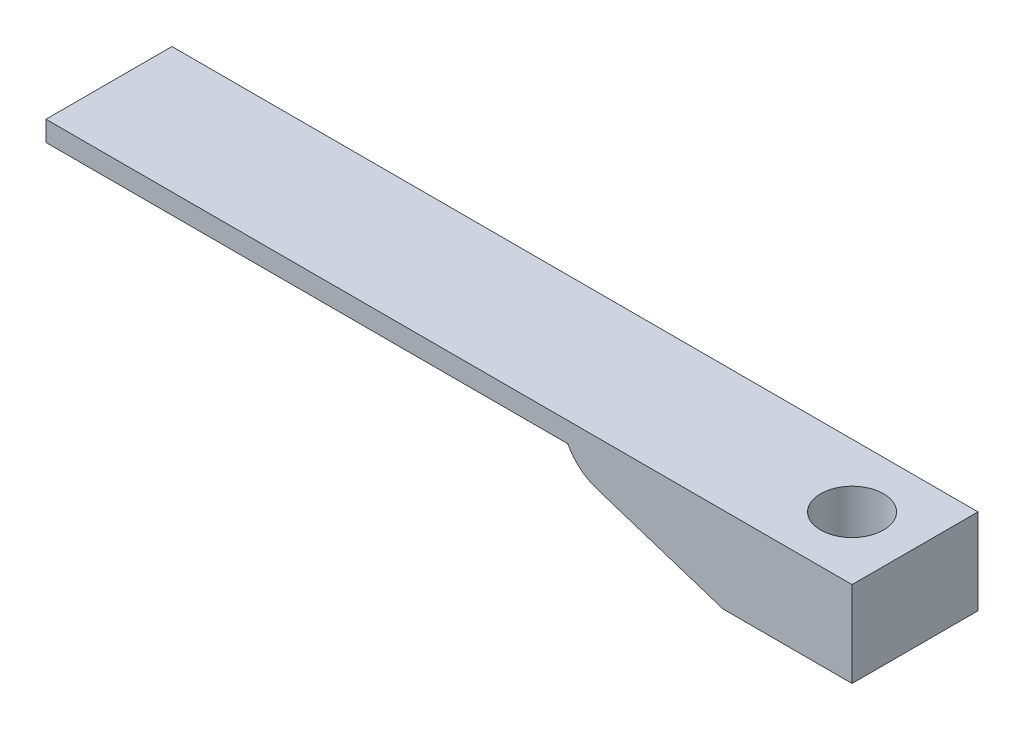
SolidWorks part; units mm, degrees
ref_plane "Front Plane" through (0, 0, 0) normal (0, 0, 1) x (1, 0, 0)
ref_plane "Top Plane" through (0, 0, 0) normal (0, 1, 0) x (1, 0, 0)
ref_plane "Right Plane" through (0, 0, 0) normal (1, 0, 0) x (0, 0, -1)
sketch "Sketch1" plane through (0, 0, 0) normal (0, 1, 0) x (1, 0, 0)
  line L1 (-80, 12.5) -> (80, 12.5)
  line L2 (-80, 12.5) -> (-80, -12.5)
  line L3 (-80, -12.5) -> (80, -12.5)
  line L4 (80, 12.5) -> (80, -12.5)
  line L5 (-80, 12.5) -> (80, -12.5) construction
  line L6 (-80, -12.5) -> (80, 12.5) construction
  circle A4 centre (67.5, 0) radius 6.25
  point P0 (0, 0)
  point P17 (80, 0)
  dimension "D3" = 12.5
  dimension "D4" = 12.5
  dimension "D1" = 25
  dimension "D2" = 160
extrude "Boss-Extrude1" add sketch "Sketch1" along normal blind 4 contours L3 L4 L1 L2 A4 | L3 region at (-2.1364, 0, 0)
sketch "Sketch2" plane through (0, 0, 0) normal (0, -1, 0) x (1, 0, 0)
  line L0 (23.59, 12.5) -> (23.59, -12.5)
  line L1 (-80, 12.5) -> (80, 12.5) construction
  line L2 (-80, -12.5) -> (80, -12.5) construction
  line L3 (23.59, 12.5) -> (80, 12.5)
  line L4 (80, 12.5) -> (80, -12.5)
  line L5 (80, -12.5) -> (80, 12.5) construction
  line L6 (80, -12.5) -> (23.59, -12.5)
  circle A0 centre (67.5, 0) radius 6.25
  circle M3 centre (67.5, 0) radius 6.25
  line M4 (80, -12.5) -> (80, 12.5)
  line M5 (80, 12.5) -> (-80, 12.5)
  line M7 (-80, -12.5) -> (80, -12.5)
  dimension "D1" = 56.41
extrude "Boss-Extrude2" add sketch "Sketch2" along normal blind 13 contours L0 M5 M7 M4 M3 region at (50.2981, 0, 0)
chamfer "Chamfer1" distance 10 angle 72 1 edges at (23.59, -13, 0) first distance on face at (23.59, -6.5, 0)
fillet "Fillet1" radius 10 1 edges at (23.59, -3, 0)
